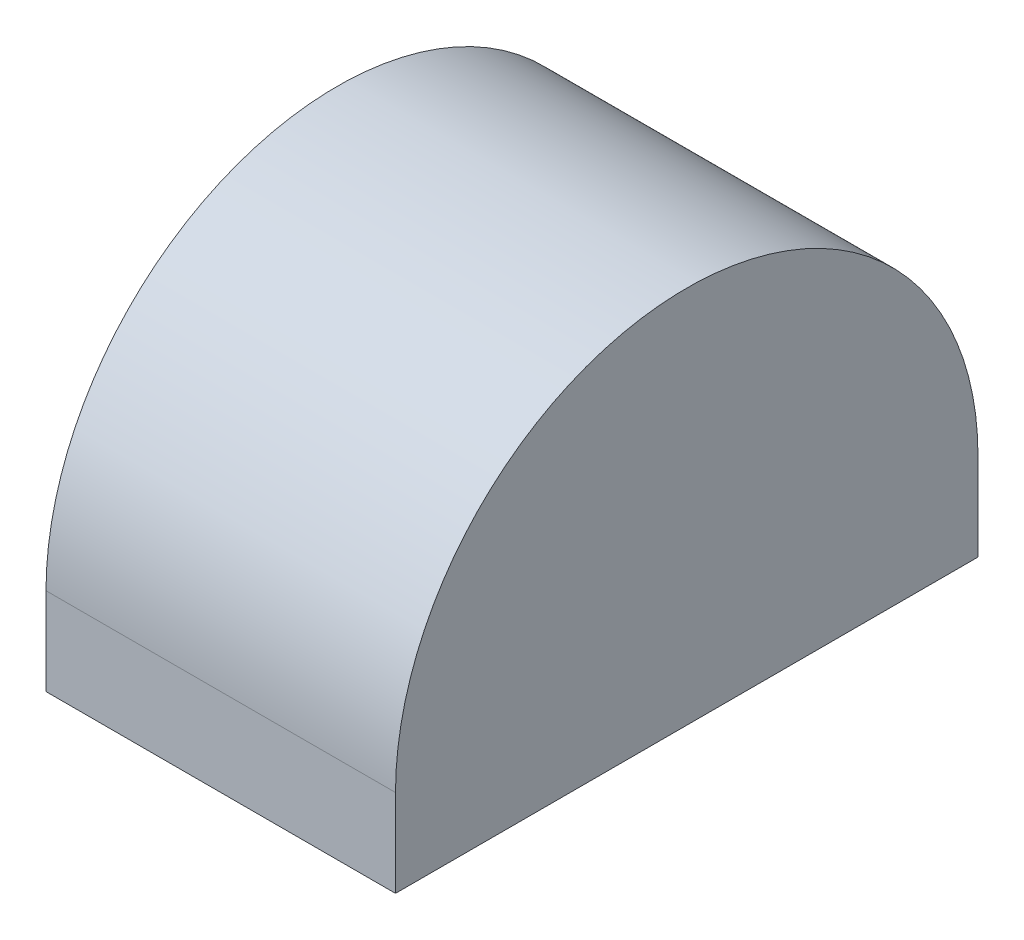
SolidWorks part; units mm, degrees
ref_plane "Front Plane" through (0, 0, 0) normal (0, 0, 1) x (1, 0, 0)
ref_plane "Top Plane" through (0, 0, 0) normal (0, 1, 0) x (1, 0, 0)
ref_plane "Right Plane" through (0, 0, 0) normal (1, 0, 0) x (0, 0, -1)
sketch "Sketch1" plane through (0, 0, 0) normal (1, 0, 0) x (0, 0, -1)
  line L0 (0, 0) -> (0, 3)
  line L1 (0, 0) -> (20, 0)
  line L2 (20, 0) -> (20, 3)
  arc A0 (0, 3) -> (20, 3) centre (10, 3) cw
  dimension "D1" = 3
  dimension "D2" = 20
extrude "Boss-Extrude1" add sketch "Sketch1" along normal mid plane 12
sketch "Sketch2" plane through (0, 0, 0) normal (1, 0, 0) x (0, 0, -1)
  line L0 (10, 0) -> (17.5, 0)
  line L1 (0, 0) -> (20, 0) construction
  line L2 (17.5, 0) -> (17.5, 3)
  line L3 (10, 0) -> (10, 11.5) construction
  line L4 (10, 11.5) -> (13.8888, 9.2548)
  line L5 (10, 11.5) -> (6.1112, 9.2548)
  line L6 (10, 0) -> (2.5, 0)
  line L7 (2.5, 0) -> (2.5, 3)
  line L8 (0, 3) -> (0, 0) construction
  arc A0 (20, 3) -> (0, 3) centre (10, 3) ccw construction
  arc A1 (2.5, 3) -> (6.1112, 9.2548) centre (9.7224, 3) cw
  arc A2 (13.8888, 9.2548) -> (17.5, 3) centre (10.2776, 3) cw
  point P13 (10, 13)
  point P15 (18.0612, 1.6367)
  point P17 (0, 0)
  point P20 (2.5, 1.7258)
  dimension "D1" = 1.5
  dimension "D2" = 60
  dimension "D3" = 60
  dimension "D4" = 2.5
extrude "Cut-Extrude1" cut sketch "Sketch2" against normal mid plane 7
